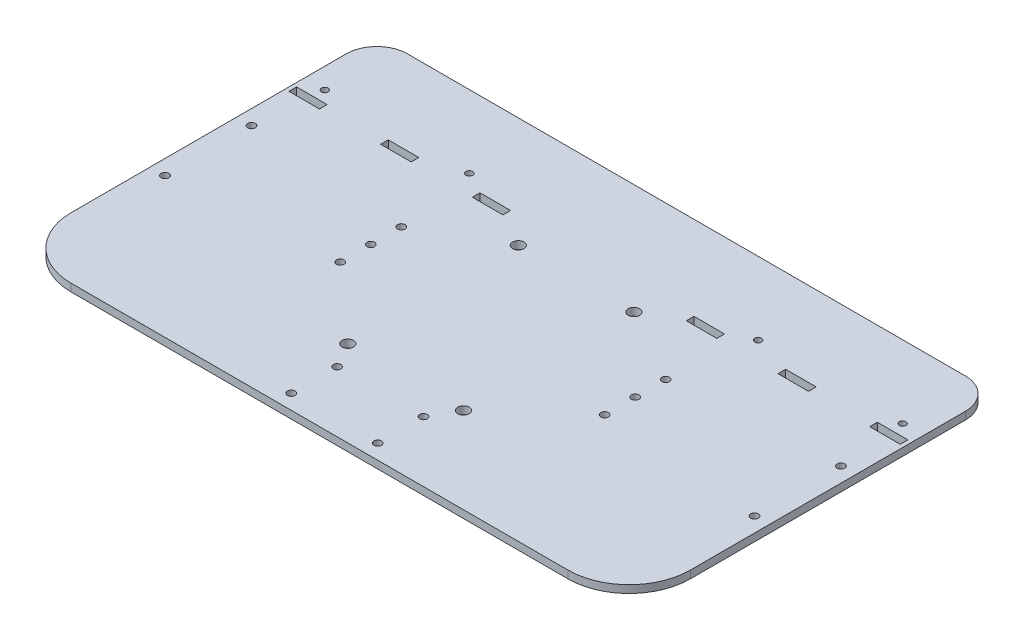
SolidWorks part; units mm, degrees
ref_plane "Front Plane" through (0, 0, 0) normal (0, 0, 1) x (1, 0, 0)
ref_plane "Top Plane" through (0, 0, 0) normal (0, 1, 0) x (1, 0, 0)
ref_plane "Right Plane" through (0, 0, 0) normal (1, 0, 0) x (0, 0, -1)
sketch "Sketch1" plane through (0, 0, 0) normal (0, 1, 0) x (1, 0, 0)
  line L0 (257.2387, -695.2) -> (257.2387, 49304.8) construction
  line L1 (50.8, 0) -> (463.6775, 0)
  line L2 (0, 50.8) -> (0, 279.4)
  line L3 (25.4, 304.8) -> (489.0775, 304.8)
  line L4 (514.4775, 50.8) -> (514.4775, 279.4)
  line L5 (511.1755, 228.5746) -> (485.7755, 228.5746)
  line L6 (511.1755, 228.5746) -> (511.1755, 234.9246)
  line L7 (511.1755, 234.9246) -> (485.7755, 234.9246)
  line L8 (485.7755, 228.5746) -> (485.7755, 234.9246)
  line L9 (434.9755, 228.5746) -> (409.5755, 228.5746)
  line L10 (434.9755, 228.5746) -> (434.9755, 234.9246)
  line L11 (434.9755, 234.9246) -> (409.5755, 234.9246)
  line L12 (409.5755, 228.5746) -> (409.5755, 234.9246)
  line L13 (358.7755, 228.5746) -> (333.3755, 228.5746)
  line L14 (358.7755, 228.5746) -> (358.7755, 234.9246)
  line L15 (358.7755, 234.9246) -> (333.3755, 234.9246)
  line L16 (333.3755, 228.5746) -> (333.3755, 234.9246)
  line L17 (180.9755, 228.5746) -> (155.5755, 228.5746)
  line L18 (180.9755, 228.5746) -> (180.9755, 234.9246)
  line L19 (180.9755, 234.9246) -> (155.5755, 234.9246)
  line L20 (155.5755, 228.5746) -> (155.5755, 234.9246)
  line L21 (104.7755, 228.5746) -> (79.3755, 228.5746)
  line L22 (104.7755, 228.5746) -> (104.7755, 234.9246)
  line L23 (104.7755, 234.9246) -> (79.3755, 234.9246)
  line L24 (79.3755, 228.5746) -> (79.3755, 234.9246)
  line L25 (28.5755, 228.5746) -> (3.1755, 228.5746)
  line L26 (28.5755, 228.5746) -> (28.5755, 234.9246)
  line L27 (28.5755, 234.9246) -> (3.1755, 234.9246)
  line L28 (3.1755, 228.5746) -> (3.1755, 234.9246)
  line L29 (147.3962, 215.8746) -> (147.3962, 88.8746) construction
  line L30 (156.0962, 215.8746) -> (138.6962, 215.8746) construction
  line L31 (156.0962, 88.8746) -> (138.6962, 88.8746) construction
  circle A0 centre (305.327, 213.0551) radius 4.7625
  circle A1 centre (305.327, 71.4251) radius 4.7625
  circle A2 centre (502.1739, 116.4574) radius 3.175
  circle A3 centre (502.1739, 188.2918) radius 3.175
  circle A4 centre (12.3031, 116.4574) radius 3.175
  circle A5 centre (12.3031, 188.2918) radius 3.175
  circle A6 centre (209.277, 71.4251) radius 4.7625
  circle A7 centre (209.277, 213.0551) radius 4.7625
  circle A8 centre (221.3848, 50.4031) radius 3.175
  circle A9 centre (221.3848, 12.3031) radius 3.175
  circle A10 centre (293.2192, 50.4031) radius 3.175
  circle A11 centre (293.2192, 12.3031) radius 3.175
  circle A12 centre (147.3962, 177.7746) radius 3.175
  circle A13 centre (147.3962, 126.9746) radius 3.175
  circle A14 centre (147.3962, 152.3746) radius 3.175
  circle A15 centre (367.0813, 152.3746) radius 3.175
  circle A16 centre (367.0813, 126.9746) radius 3.175
  circle A17 centre (367.0813, 177.7746) radius 3.175
  circle A18 centre (497.1755, 244.4496) radius 2.794
  circle A19 centre (377.1755, 244.4496) radius 2.794
  circle A20 centre (137.1755, 244.4496) radius 2.794
  circle A21 centre (17.1755, 244.4496) radius 2.794
  arc A22 (463.6775, 0) -> (514.4775, 50.8) centre (463.6775, 50.8) ccw
  arc A23 (50.8, 0) -> (0, 50.8) centre (50.8, 50.8) cw
  arc A24 (0, 279.4) -> (25.4, 304.8) centre (25.4, 279.4) cw
  arc A25 (489.0775, 304.8) -> (514.4775, 279.4) centre (489.0775, 279.4) cw
  point P92 (257.2387, 304.8)
  point P119 (0, 0)
  dimension "D1" = 50.8
  dimension "D2" = 50.8
  dimension "D3" = 25.4
extrude "Boss-Extrude1" add sketch "Sketch1" along normal blind 6.35
